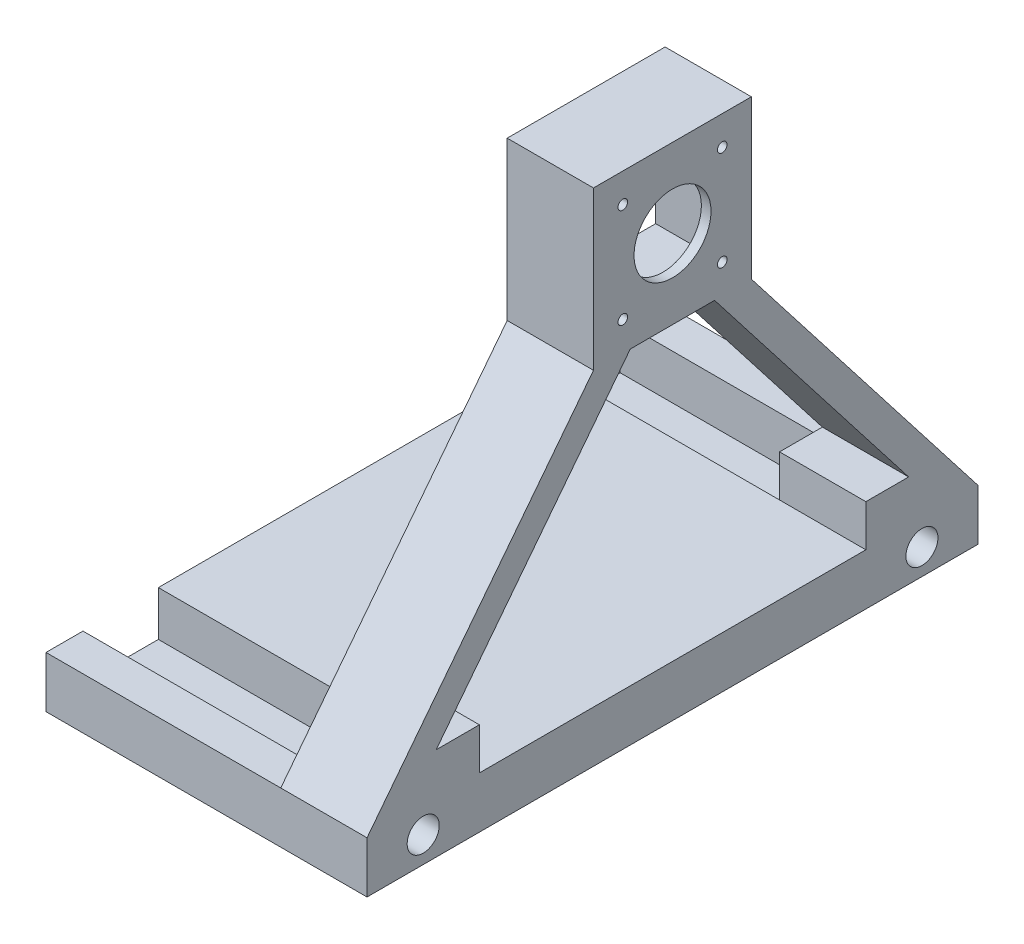
SolidWorks part; units mm, degrees
ref_plane "Front Plane" through (0, 0, 0) normal (0, 0, 1) x (1, 0, 0)
ref_plane "Top Plane" through (0, 0, 0) normal (0, 1, 0) x (1, 0, 0)
ref_plane "Right Plane" through (0, 0, 0) normal (1, 0, 0) x (0, 0, -1)
sketch "Sketch1" plane through (0, 0, 0) normal (0, 1, 0) x (1, 0, 0)
  line L1 (-41.4675, -30.6477) -> (85.5325, -30.6477)
  line L2 (-41.4675, -30.6477) -> (-41.4675, 159.8523)
  line L3 (-41.4675, 159.8523) -> (85.5325, 159.8523)
  line L4 (85.5325, -30.6477) -> (85.5325, 159.8523)
  dimension "D1" = 127
  dimension "D2" = 190.5
extrude "Boss-Extrude1" add sketch "Sketch1" along normal blind 16
sketch "Sketch3" plane through (0, 16, 0) normal (0, 1, 0) x (1, 0, 0)
  line L0 (85.5325, -30.6477) -> (85.5325, 159.8523) construction
  line L1 (-14.5675, 159.8523) -> (58.6325, 159.8523)
  line L2 (-14.5675, 159.8523) -> (-14.5675, -30.6477)
  line L3 (-14.5675, -30.6477) -> (58.6325, -30.6477)
  line L4 (58.6325, 159.8523) -> (58.6325, -30.6477)
  line L5 (-41.4675, 159.8523) -> (-41.4675, -30.6477) construction
  line L6 (-41.4675, -30.6477) -> (85.5325, -30.6477) construction
  line L7 (85.5325, 159.8523) -> (-41.4675, 159.8523) construction
  dimension "D1" = 26.9
  dimension "D2" = 26.9
  dimension "D3" = 0
  dimension "D4" = 0
extrude "Cut-Extrude2" cut sketch "Sketch3" against normal offset from surface (14 mm away) 2 up to face at (22.0325, 0, -64.6023)
sketch "Sketch6" plane through (0, 2, 0) normal (0, 1, 0) x (1, 0, 0)
  line L0 (58.6325, -30.6477) -> (58.6325, 159.8523) construction
  line L1 (58.6325, 124.882) -> (-14.5675, 124.882)
  line L2 (58.6325, 124.882) -> (58.6325, 4.382)
  line L3 (58.6325, 4.382) -> (-14.5675, 4.382)
  line L4 (-14.5675, 124.882) -> (-14.5675, 4.382)
  line L5 (-14.5675, 159.8523) -> (-14.5675, -30.6477) construction
  line L6 (58.6325, -30.6477) -> (58.6325, 159.8523) construction
  line L7 (-14.5675, 159.8523) -> (58.6325, 159.8523)
  line L8 (-14.5675, 159.8523) -> (-14.5675, 148.382)
  line L9 (-14.5675, 148.382) -> (58.6325, 148.382)
  line L10 (58.6325, 159.8523) -> (58.6325, 148.382)
  line L11 (-14.5675, -30.6477) -> (58.6325, -30.6477)
  line L12 (-14.5675, -30.6477) -> (-14.5675, -19.118)
  line L13 (-14.5675, -19.118) -> (58.6325, -19.118)
  line L14 (58.6325, -30.6477) -> (58.6325, -19.118)
  dimension "D1" = 23.5
  dimension "D2" = 23.5
extrude "Boss-Extrude5" add sketch "Sketch6" along normal up to surface (14 mm away) up to face at (-28.0175, 16, -64.6023)
sketch "Sketch9" plane through (-41.4675, 0, 0) normal (-1, 0, 0) x (0, 0, 1)
  line L0 (-159.8523, 16) -> (30.6477, 16) construction
  line L1 (-86.2523, 153.2346) -> (-42.9523, 153.2346)
  line L2 (-86.2523, 153.2346) -> (-86.2523, 109.9346)
  line L3 (-86.2523, 109.9346) -> (-42.9523, 109.9346)
  line L4 (-42.9523, 153.2346) -> (-42.9523, 109.9346)
  line L5 (-89.2523, 156.2346) -> (-39.9523, 156.2346)
  line L6 (-39.9523, 156.2346) -> (-39.9523, 106.9346)
  line L7 (-89.2523, 106.9346) -> (-39.9523, 106.9346)
  line L8 (-89.2523, 156.2346) -> (-89.2523, 106.9346)
  line L9 (-89.2523, 106.9346) -> (-159.8523, 16)
  line L10 (-159.8523, 16) -> (30.6477, 16)
  line L11 (30.6477, 16) -> (-39.9523, 106.9346)
  line L12 (-148.382, 16) -> (-77.782, 106.9346)
  line L13 (19.118, 16) -> (-51.482, 106.9346)
  line L14 (-80.2523, 115.9346) -> (-48.9523, 115.9346)
  line L15 (-48.9523, 147.2346) -> (-48.9523, 115.9346)
  line L16 (-80.2523, 147.2346) -> (-48.9523, 147.2346)
  line L17 (-80.2523, 147.2346) -> (-80.2523, 115.9346)
  circle A1 centre (-64.6023, 131.5846) radius 12
  point P4 (-64.6023, 109.9346)
  point P5 (-64.6023, 16)
  point P19 (-86.2523, 131.5846)
  line M11 (30.6477, 16) -> (-159.8523, 16)
  dimension "D3" = 6
  dimension "D6" = 24
  dimension "D1" = 43.3
  dimension "D2" = 3
  dimension "D4" = 11.4704
  dimension "D5" = 11.5296
extrude "Boss-Extrude7" add sketch "Sketch9" against normal up to surface (26.9 mm away) contours L10 L12 L7 L9 | L5 L8 L7 L6 L1 L4 L3 L2 | L13 L11 L7 M11 region at (-41.4675, 155.5374, -64.6023) region at (-41.4675, 61.4673, -118.8171) region at (-41.4675, 61.4673, -10.4171) up to face at (-14.5675, 9, -136.632)
extrude "Boss-Extrude8" add sketch "Sketch9<5>" against normal blind 3 contours L4 L1 L2 L3 L17 L16 L15 L14 | L16 L17 L14 L15 A1 region at (-41.4675, 152.6223, -64.6023) region at (-41.4675, 131.5846, -79.8097)
sketch "Sketch9<5>" plane through (-41.4675, 0, 0) normal (-1, 0, 0) x (0, 0, 1) same geometry as "Sketch9"
sketch "Sketch10" plane through (85.5325, 0, 0) normal (1, 0, 0) x (0, 0, -1)
  line L0 (42.9523, 153.2346) -> (86.2523, 153.2346)
  line L1 (42.9523, 153.2346) -> (42.9523, 109.9346)
  line L2 (42.9523, 109.9346) -> (86.2523, 109.9346)
  line L3 (86.2523, 153.2346) -> (86.2523, 109.9346)
  line L4 (39.9523, 156.175) -> (89.1927, 156.175)
  line L5 (89.1927, 156.175) -> (89.1927, 106.9346)
  line L6 (39.9523, 106.9346) -> (89.1927, 106.9346)
  line L7 (39.9523, 156.175) -> (39.9523, 106.9346)
  line L8 (39.9523, 106.9346) -> (-30.6477, 16)
  line L9 (-30.6477, 16) -> (159.7927, 16)
  line L10 (159.7927, 16) -> (89.1927, 106.9346)
  line L11 (-19.1773, 16) -> (51.4227, 106.9346)
  line L12 (148.3227, 16) -> (77.7227, 106.9346)
  line L13 (48.9523, 115.9346) -> (80.2523, 115.9346)
  line L14 (80.2523, 147.2346) -> (80.2523, 115.9346)
  line L15 (48.9523, 147.2346) -> (80.2523, 147.2346)
  line L16 (48.9523, 147.2346) -> (48.9523, 115.9346)
  circle A0 centre (64.6023, 131.5846) radius 12
  point P4 (64.6023, 109.9346)
  point P15 (42.9523, 131.5846)
  dimension "D12" = 24
  dimension "D1" = 11.4704
  dimension "D2" = 11.47
  dimension "D3" = 3
  dimension "D4" = 6
  dimension "D5" = 15.65
  dimension "D6" = 115.1237
  dimension "D7" = 115.1237
  dimension "D8" = 190.4404
  dimension "D9" = 6
  dimension "D10" = 2.9404
  dimension "D11" = 15.65
extrude "Boss-Extrude11" add sketch "Sketch10" against normal up to surface (26.9 mm away) contours L9 L11 L6 L8 | L12 L2 L10 L6 | L4 L7 L6 L5 L0 L3 L2 L1 region at (85.5325, 155.4786, -64.5725) region at (85.5325, 61.4673, -10.3875) region at (85.5325, 61.4673, -118.7577) up to face at (58.6325, 9, -136.632)
extrude "Boss-Extrude12" add sketch "Sketch10<5>" against normal blind 3 contours L3 L0 L1 L2 L16 L15 L14 L13 | L15 L16 L13 L14 A0 region at (85.5325, 152.6223, -64.6023) region at (85.5325, 131.5846, -49.395)
sketch "Sketch10<5>" plane through (85.5325, 0, 0) normal (1, 0, 0) x (0, 0, -1) same geometry as "Sketch10"
sketch "Sketch12" plane through (-38.4675, 0, 0) normal (1, 0, 0) x (0, 0, -1)
  line L4 (42.9523, 153.2346) -> (42.9523, 109.9346)
  line L5 (42.9523, 153.2346) -> (42.9523, 109.9346)
  line L6 (42.9523, 109.9346) -> (86.2523, 109.9346)
  line L7 (42.9523, 109.9346) -> (86.2523, 109.9346)
  line L8 (86.2523, 109.9346) -> (86.2523, 153.2346)
  line L9 (86.2523, 109.9346) -> (86.2523, 153.2346)
  line L10 (86.2523, 153.2346) -> (42.9523, 153.2346)
  line L11 (86.2523, 153.2346) -> (42.9523, 153.2346)
  circle A0 centre (80.1023, 147.0846) radius 1.5 construction
  circle A1 centre (80.1023, 147.0846) radius 1.5
  circle A2 centre (49.1023, 147.0846) radius 1.5 construction
  circle A3 centre (49.1023, 116.0846) radius 1.5 construction
  circle A4 centre (80.1023, 116.0846) radius 1.5 construction
  circle A5 centre (49.1023, 147.0846) radius 1.5
  circle A6 centre (49.1023, 116.0846) radius 1.5
  circle A7 centre (80.1023, 116.0846) radius 1.5
  dimension "D1" = 0
extrude "Cut-Extrude4" cut sketch "Sketch12" along normal up to surface (124 mm away) contours A7 | A6 | A5 | A1 up to face at (85.5325, 61.4673, -64.5727)
sketch "Sketch13" plane through (0, 16, 0) normal (0, 1, 0) x (1, 0, 0)
  line L1 (-14.5675, 124.882) -> (-41.4675, 124.882)
  line L2 (-14.5675, 124.882) -> (-14.5675, 148.382)
  line L3 (-14.5675, 148.382) -> (-41.4675, 148.382)
  line L4 (-41.4675, 124.882) -> (-41.4675, 148.382)
  line L5 (-14.5675, 4.382) -> (-41.4675, 4.382)
  line L6 (-14.5675, 4.382) -> (-14.5675, -19.118)
  line L7 (-14.5675, -19.118) -> (-41.4675, -19.118)
  line L8 (-41.4675, 4.382) -> (-41.4675, -19.118)
  line L9 (58.6325, 4.382) -> (85.5325, 4.382)
  line L10 (58.6325, 4.382) -> (58.6325, -19.1773)
  line L11 (58.6325, -19.1773) -> (85.5325, -19.1773)
  line L12 (85.5325, 4.382) -> (85.5325, -19.1773)
  line L13 (58.6325, 124.882) -> (85.5325, 124.882)
  line L14 (58.6325, 124.882) -> (58.6325, 148.3227)
  line L15 (58.6325, 148.3227) -> (85.5325, 148.3227)
  line L16 (85.5325, 124.882) -> (85.5325, 148.3227)
extrude "Boss-Extrude13" add sketch "Sketch13" along normal blind 13
sketch "cut line" plane through (85.5325, 0, 0) normal (1, 0, 0) x (0, 0, -1)
  line L0 (-30.5884, 16) -> (159.8523, 16)
  point P3 (64.632, 16)
sketch "Sketch16" plane through (0, 29, 0) normal (0, 1, 0) x (1, 0, 0)
  line L0 (85.5325, -9.0844) -> (85.5325, 4.382) construction
  line L1 (85.5325, 4.382) -> (58.6325, 4.382) construction
  line L2 (58.6325, 4.382) -> (58.6325, -9.0844) construction
  line L3 (58.6325, 4.382) -> (58.6325, -9.0844) construction
  line L4 (58.6325, -9.0844) -> (85.5325, -9.0844) construction
  line L5 (72.0825, -9.0844) -> (58.6325, -9.0844) construction
  line L6 (65.3575, -9.0844) -> (65.3575, 4.382) construction
  line L7 (78.8075, -9.0844) -> (78.8075, 4.382) construction
  line L8 (85.5325, -2.3512) -> (58.6325, -2.3512) construction
  line L9 (85.5325, 124.882) -> (58.6325, 124.882) construction
  line L10 (58.6325, 124.882) -> (58.6325, 138.2297) construction
  line L11 (85.5325, 138.2297) -> (58.6325, 138.2297) construction
  line L12 (85.5325, -9.0844) -> (72.0825, -9.0844) construction
  line L13 (72.0825, -9.0844) -> (85.5325, -9.0844) construction
  line L14 (58.6325, 138.2297) -> (58.6325, 124.882) construction
  line L15 (-14.5675, 124.882) -> (-41.4675, 124.882) construction
  line L16 (-41.4675, 124.882) -> (-41.4675, 138.289) construction
  line L17 (-28.0175, -9.0251) -> (-41.4675, -9.0251) construction
  line L18 (-41.4675, 4.382) -> (-41.4675, -9.0251) construction
  line L19 (-28.0175, -9.0251) -> (-14.5675, -9.0251) construction
  line L20 (-14.5675, -9.0251) -> (-14.5675, 4.382) construction
  line L21 (-14.5675, 4.382) -> (-14.5675, -2.3216) construction
  line L23 (-28.0175, 4.382) -> (-28.0175, -9.0251) construction
  line L24 (-14.5675, 4.382) -> (-28.0175, 4.382) construction
  line L25 (-28.0175, 4.382) -> (-40.9679, 4.382) construction
  line L26 (-28.0175, -2.3216) -> (-14.5675, -2.3216) construction
  line L27 (-28.0175, -2.3216) -> (-41.4675, -2.3216) construction
  line L28 (-14.5675, -2.3216) -> (-28.0175, -2.3216) construction
  point P18 (65.3575, -2.3512)
  point P19 (78.8075, -2.3512)
  point P39 (65.3575, 131.5558)
  point P42 (78.8075, 131.5558)
  point P51 (-21.2925, -2.3216)
  point P52 (-34.7425, -2.3216)
  point P53 (-34.7425, 131.5558)
  point P54 (-21.2925, 131.5558)
sketch "Sketch23" plane through (0, 0, 0) normal (0, -1, 0) x (1, 0, 0)
  line L4 (-41.4675, 30.6477) -> (-41.4675, -159.8523)
  line L5 (-41.4675, -159.8523) -> (85.5325, -159.8523)
  line L6 (85.5325, -159.8523) -> (85.5325, 30.6477)
  line L7 (85.5325, 30.6477) -> (-41.4675, 30.6477)
  line L8 (-41.4675, 30.6477) -> (-41.4675, -159.8523)
  line L9 (-41.4675, -159.8523) -> (85.5325, -159.8523)
  line L10 (85.5325, -159.8523) -> (85.5325, 30.6477)
  line L11 (85.5325, 30.6477) -> (-41.4675, 30.6477)
  point P2 (65.3575, 2.3512)
  point P5 (78.8075, 2.3512)
  point P8 (65.3575, -131.5558)
  point P10 (78.8075, -131.5558)
  point P12 (-21.2925, -131.5558)
  point P14 (-34.7425, -131.5558)
  point P16 (-34.7425, 2.3216)
  point P18 (-21.2925, 2.3216)
  dimension "D1" = 0
hole_wizard "CBORE for M4 Pan Head Machine Screw1" positions "Sketch25" profile "Sketch24" counterbore size "M4" standard "ANSI Metric"
sketch "Sketch25" plane through (0, 0, 0) normal (0, -1, 0) x (-1, 0, 0)
  point P0 (21.2925, -2.3216)
  point P3 (34.7425, -2.3216)
  point P6 (-65.3575, -2.3512)
  point P9 (-78.8075, -2.3512)
  point P12 (-78.8075, 131.5558)
  point P15 (-65.3575, 131.5558)
  point P18 (21.2925, 131.5558)
  point P21 (34.7425, 131.5558)
sketch "Sketch24" plane through (-21.2925, 0, 2.3216) normal (1, 0, 0) x (0, 0, -1)
  line L0 (0, 0) -> (0, 26.2919)
  line L1 (0, 26.2919) -> (2.15, 25)
  line L2 (2.15, 25) -> (2.15, 3.1)
  line L3 (2.15, 3.1) -> (4.5, 3.1)
  line L5 (4.5, 3.1) -> (4.5, 0.046)
  line L6 (4.5, 0.046) -> (4.525, 0)
  line L7 (4.525, 0) -> (0, 0)
  line L8 (-4.5, 0.046) -> (-4.525, 0) construction
  line L10 (0, 26.2919) -> (-2.15, 25) construction
  line L11 (0, -6.35) -> (0, 107.95) construction
  dimension "Hole Dia." = 4.3
  dimension "Hole Depth" = 25
  dimension "C'Bore Dia." = 9
  dimension "C'Bore Depth" = 3.1
  dimension "Near C'Sink Dia." = 9.05
  dimension "Near C'Sink Angle" = 57
  dimension "Drill Angle" = 118
sketch "Sketch27" plane through (-41.4675, 0, 0) normal (-1, 0, 0) x (0, 0, 1)
  circle A0 centre (-142.3671, 8) radius 5
  circle A1 centre (13.1329, 8.094) radius 5
  point P10 (13.1329, 16)
  point P11 (30.5793, 8.094)
  point P14 (-142.3671, 16)
  point P15 (-159.8523, 8)
  point P16 (-142.3671, 8)
  point P17 (13.1329, 8.094)
  dimension "D1" = 10
extrude "Cut-Extrude8" cut sketch "Sketch27" against normal up to surface (127 mm away) up to face at (85.5325, 45.2337, -64.6023)
sketch "Sketch28" plane through (0, 0, 30.6477) normal (0, 0, 1) x (1, 0, 0)
  line L0 (-14.5675, 16) -> (-14.5675, 0)
split "Split1" trim tools "Sketch28" bodies to split 135 resulting bodies 136
